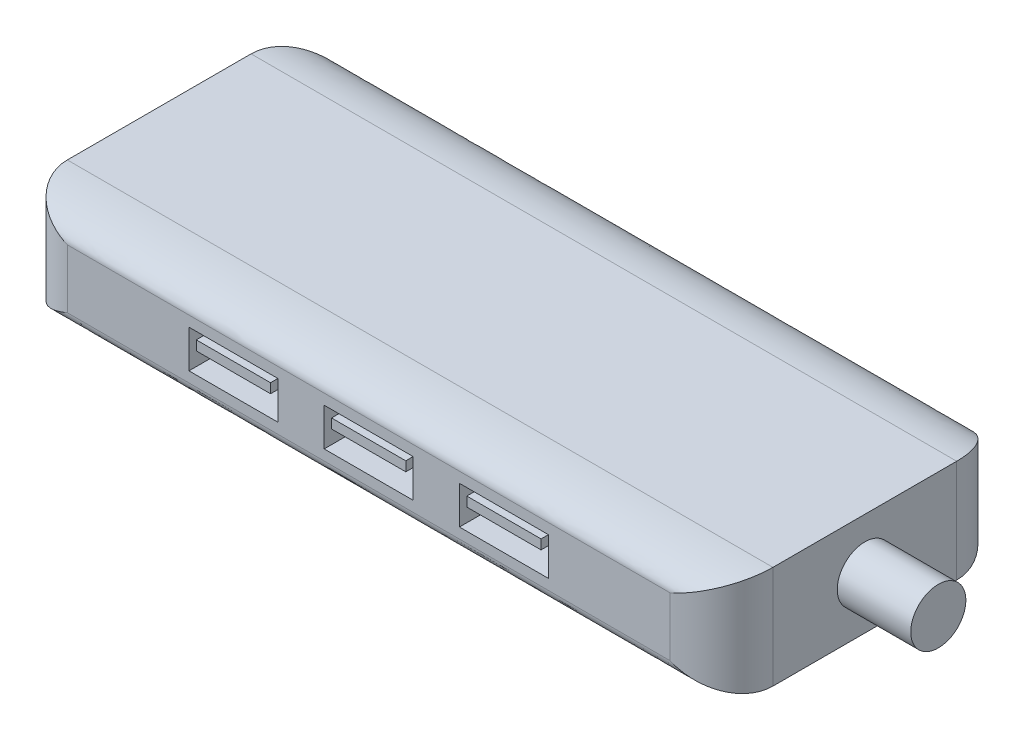
SolidWorks part; units mm, degrees
ref_plane "Płaszczyzna przednia" through (0, 0, 0) normal (0, 0, 1) x (1, 0, 0)
ref_plane "Płaszczyzna górna" through (0, 0, 0) normal (0, 1, 0) x (1, 0, 0)
ref_plane "Płaszczyzna prawa" through (0, 0, 0) normal (1, 0, 0) x (0, 0, -1)
sketch "Szkic1" plane through (0, 0, 0) normal (0, 1, 0) x (1, 0, 0)
  line L1 (-48, -19.5) -> (48, -19.5)
  line L2 (-48, -19.5) -> (-48, 19.5)
  line L3 (-48, 19.5) -> (48, 19.5)
  line L4 (48, -19.5) -> (48, 19.5)
  line L5 (-48, -19.5) -> (48, 19.5) construction
  line L6 (-48, 19.5) -> (48, -19.5) construction
  point P0 (0, 0)
  dimension "D1" = 96
  dimension "D2" = 39
extrude "Dodanie-wyciągnięcie1" add sketch "Szkic1" along normal blind 14
fillet "Zaokrąglenie2" radius 7 4 edges at (0, 0, -19.5) (0, 0, 19.5) (0, 14, -19.5) (0, 14, 19.5) second distance 3 first distance on face at (0, 0, 0) first distance on face at (0, 14, 0)
sketch "Szkic2" plane through (0, 14, 0) normal (0, 1, 0) x (1, 0, 0)
  line L0 (-41, 19.5) -> (41, 19.5) construction
  line L1 (-41, -19.5) -> (41, -19.5) construction
  line L2 (-48, -12.5) -> (-48, 12.5) construction
  line L3 (-41, 19.5) -> (41, 19.5) construction
  line L4 (48, -12.5) -> (48, 12.5) construction
  line L5 (-48, -19.5) -> (48, 19.5) construction
  line L6 (-48, 19.5) -> (48, -19.5) construction
  line L7 (-48, -19.5) -> (-41, -19.5)
  line L8 (-48, -19.5) -> (-48, -12.5)
  line L9 (-48, 19.5) -> (-41, 19.5)
  line L10 (48, -19.5) -> (48, -12.5)
  line L11 (-48, -19.5) -> (48, 19.5) construction
  line L12 (-48, 19.5) -> (48, -19.5) construction
  line L13 (41, 19.5) -> (48, 19.5)
  line L14 (-48, -12.5) -> (-48, 12.5) construction
  line L15 (-48, 12.5) -> (-48, 19.5)
  line L16 (-41, -19.5) -> (41, -19.5) construction
  line L17 (41, -19.5) -> (48, -19.5)
  line L18 (48, -12.5) -> (48, 12.5) construction
  line L19 (48, 12.5) -> (48, 19.5)
  arc A0 (41, -19.5) -> (48, -12.5) centre (41, -12.5) ccw
  arc A1 (-41, -19.5) -> (-48, -12.5) centre (-41, -12.5) cw
  arc A2 (-48, 12.5) -> (-41, 19.5) centre (-41, 12.5) cw
  arc A3 (41, 19.5) -> (48, 12.5) centre (41, 12.5) cw
  point P0 (0, 0)
  point P19 (0, 0)
  dimension "D1" = 7
extrude "Wytnij-wyciągnięcie1" cut sketch "Szkic2" against normal up to surface (14 mm away) up to face at (0, 0, 0)
sketch "Szkic3" plane through (48, 0, 0) normal (1, 0, 0) x (0, 0, -1)
  circle A0 centre (0, 7) radius 3.75
  dimension "D1" = 7.5
extrude "Dodanie-wyciągnięcie2" add sketch "Szkic3" along normal blind 10
sketch "Szkic4" plane through (0, 0, 0) normal (0, -1, 0) x (1, 0, 0)
  line L0 (-48, -12.5) -> (-48, 12.5) construction
  line L1 (-48, 8.5) -> (-48, -8.5)
  arc A0 (-48, -8.5) -> (-48, 8.5) centre (-48, 0) ccw
  dimension "D1" = 17
extrude "Dodanie-wyciągnięcie3" add sketch "Szkic4" along normal blind 1.1
fillet "Zaokrąglenie3" radius 8 1 edges at (-39.5, -1.1, 0)
sketch "Szkic5" plane through (-48, 0, 0) normal (-1, 0, 0) x (0, 0, 1)
  line L0 (-5.875, 10.6) -> (5.875, 10.6)
  line L1 (-12.5, 14) -> (12.5, 14) construction
  line L2 (0, 10.6) -> (0, 14) construction
  line L3 (-5.875, 10.6) -> (-5.875, 3.8)
  line L4 (-5.875, 3.8) -> (-3.15, 3.8)
  line L5 (-3.15, 3.8) -> (-3.15, 2.3)
  line L6 (-3.15, 2.3) -> (-1.65, 2.3)
  line L7 (-1.65, 2.3) -> (-1.65, 0.8)
  line L8 (-1.65, 0.8) -> (1.65, 0.8)
  line L9 (0, 0) -> (0, 0.8) construction
  line L10 (1.65, 2.3) -> (1.65, 0.8)
  line L11 (3.15, 3.8) -> (3.15, 2.3)
  line L12 (3.15, 2.3) -> (1.65, 2.3)
  line L13 (5.875, 3.8) -> (3.15, 3.8)
  line L14 (5.875, 10.6) -> (5.875, 3.8)
  point P3 (0, 10.6)
  point P14 (-1.65, 1.55)
  point P17 (1.65, 1.55)
  dimension "D1" = 3.4
  dimension "D2" = 11.75
  dimension "D3" = 6.8
  dimension "D4" = 1.65
  dimension "D5" = 1.5
  dimension "D6" = 1.5
  dimension "D7" = 1.5
extrude "Wytnij-wyciągnięcie2" cut sketch "Szkic5" against normal blind 11
sketch "Szkic6" plane through (0, 0, 19.5) normal (0, 0, 1) x (1, 0, 0)
  line L0 (0, 0) -> (0, 7) construction
  line L1 (-6.05, 9.575) -> (6.05, 9.575)
  line L2 (-6.05, 9.575) -> (-6.05, 4.425)
  line L3 (-6.05, 4.425) -> (6.05, 4.425)
  line L4 (6.05, 9.575) -> (6.05, 4.425)
  line L5 (-6.05, 9.575) -> (6.05, 4.425) construction
  line L6 (-6.05, 4.425) -> (6.05, 9.575) construction
  line L7 (0, 7) -> (41, 7) construction
  line L8 (41, 3) -> (41, 11) construction
  line L9 (0, 7) -> (0, 7.925) construction
  line L10 (-5.05, 8.575) -> (5.05, 8.575)
  line L11 (-5.05, 8.575) -> (-5.05, 7.275)
  line L12 (-5.05, 7.275) -> (5.05, 7.275)
  line L13 (5.05, 8.575) -> (5.05, 7.275)
  line L14 (-5.05, 8.575) -> (5.05, 7.275) construction
  line L15 (-5.05, 7.275) -> (5.05, 8.575) construction
  point P0 (0, 7)
  point P8 (0, 7.925)
  dimension "D1" = 5.15
  dimension "D2" = 12.1
  dimension "D3" = 1.3
  dimension "D4" = 1
  dimension "D5" = 1
extrude "Wytnij-wyciągnięcie3" cut sketch "Szkic6" against normal blind 9.75
pattern_linear "Szyk liniowy1" count 2 spacing 18.4 along (-1, 0, 0) of "Wytnij-wyciągnięcie3"
mirror "Lustro1" about plane through (0, 0, 0) normal (1, 0, 0) of "Szyk liniowy1"
